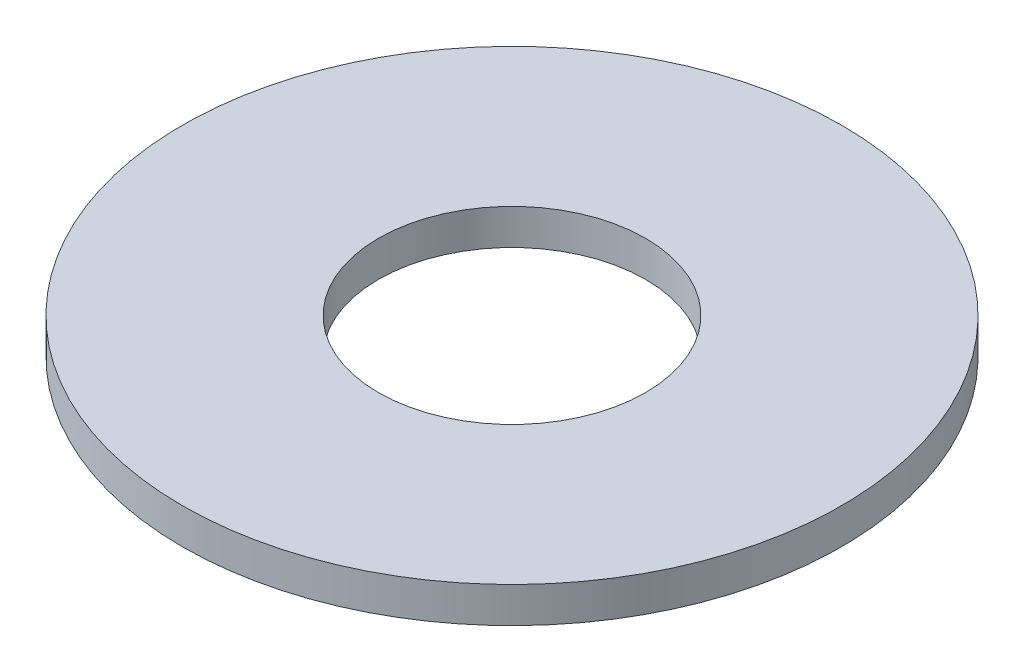
SolidWorks part; units mm, degrees
ref_plane "Front Plane" through (0, 0, 0) normal (0, 0, 1) x (1, 0, 0)
ref_plane "Top Plane" through (0, 0, 0) normal (0, 1, 0) x (1, 0, 0)
ref_plane "Right Plane" through (0, 0, 0) normal (1, 0, 0) x (0, 0, -1)
sketch "Sketch1" plane through (0, 0, 0) normal (0, 1, 0) x (1, 0, 0)
  circle A0 centre (0, 0) radius 92.5
  dimension "FLANGE_OD" = 185
extrude "Boss-Extrude1" add sketch "Sketch1" along normal blind 10
sketch "Sketch2" plane through (0, 0, 0) normal (0, 1, 0) x (1, 0, 0)
  circle A0 centre (0, 0) radius 37.5
  dimension "BORE_D" = 75
extrude "Cut-Extrude1" cut sketch "Sketch2" along normal through all
sketch "Sketch3" plane through (0, 10, 0) normal (0, 1, 0) x (1, 0, 0)
  circle A0 centre (0, 0) radius 30.8281 construction
  circle A1 centre (-30.8281, 0) radius 2.6424
  dimension "BOLT_D" = 5.2849
  dimension "BOLT_PCD" = 61.6563
extrude "Cut-Extrude2" cut sketch "Sketch3" against normal blind 6.8684 rebuild error yes
pattern_circular "CirPattern1" count 4 over 360 rebuild error yes
